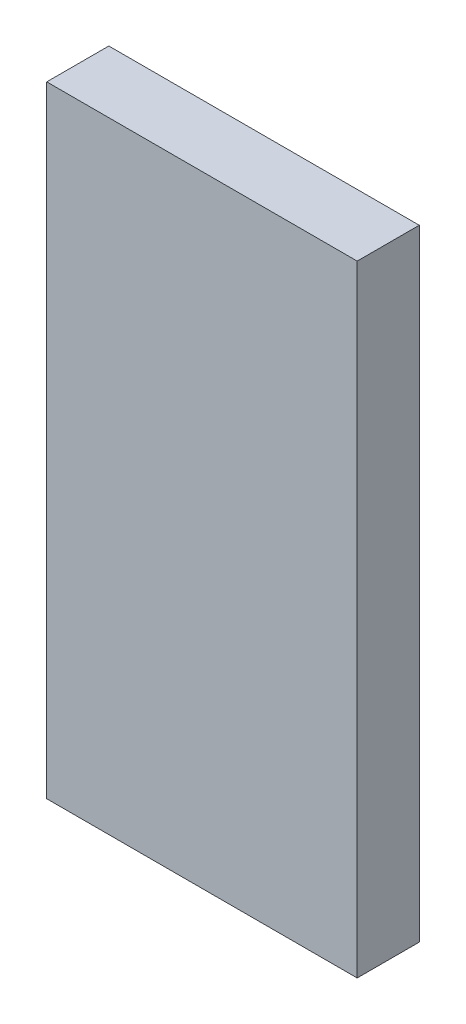
SolidWorks part; units mm, degrees
ref_plane "Front Plane" through (0, 0, 0) normal (0, 0, 1) x (1, 0, 0)
ref_plane "Top Plane" through (0, 0, 0) normal (0, 1, 0) x (1, 0, 0)
ref_plane "Right Plane" through (0, 0, 0) normal (1, 0, 0) x (0, 0, -1)
sketch "Sketch1" plane through (0, 0, 0) normal (0, 0, 1) x (1, 0, 0)
  line L0 (-94.0126, 25.3184) -> (-94.0126, -14.6816)
  line L1 (-103.0228, 45.3184) -> (-63.0228, 45.3184)
  line L2 (-103.0228, 45.3184) -> (-103.0228, -34.6816)
  line L3 (-103.0228, -34.6816) -> (-63.0228, -34.6816)
  line L4 (-63.0228, 45.3184) -> (-63.0228, -34.6816)
  line L5 (-94.0126, -14.6816) -> (-74.0126, -14.6816)
  line L6 (-74.0126, -14.6816) -> (-74.0126, 5.3184)
  line L7 (-74.0126, 5.3184) -> (-94.0126, 25.3184)
  circle A0 centre (-61.2778, 47.4217) radius 4
  circle A1 centre (-61.2778, 47.4217) radius 15 construction
  dimension "D2" = 8
  dimension "D3" = 30
  dimension "D1" = 45
  dimension "D4" = 80
  dimension "D5" = 20
  dimension "D6" = 20
  dimension "D7" = 20
  dimension "D8" = 40
extrude "Boss-Extrude1" add sketch "Sketch1" along normal blind 8 contours L1 L4 L3 L2
extrude "Cut-Extrude-Thin1" cut sketch "Sketch1<4>" along normal blind 6 thin contours L6 L7 L0 L5 thin type mid plane wall 6
sketch "Sketch1<4>" plane through (0, 0, 0) normal (0, 0, 1) x (1, 0, 0) same geometry as "Sketch1"
sketch "Sketch2" plane through (-32.2258, -32.2258, 0) normal (-0.7071, -0.7071, 0) x (0, 0, 1)
  line L4 (0, 91.6224) -> (0, 54.8529)
  line L5 (0, 54.8529) -> (6, 54.8529)
  line L6 (6, 54.8529) -> (6, 91.6224)
  line L7 (6, 91.6224) -> (0, 91.6224)
  line L8 (0, 91.6224) -> (0, 54.8529)
  line L9 (0, 54.8529) -> (6, 54.8529)
  line L10 (6, 54.8529) -> (6, 91.6224)
  line L11 (6, 91.6224) -> (0, 91.6224)
  dimension "D1" = 0
extrude "Cut-Extrude1" cut sketch "Sketch2" against normal blind 3
